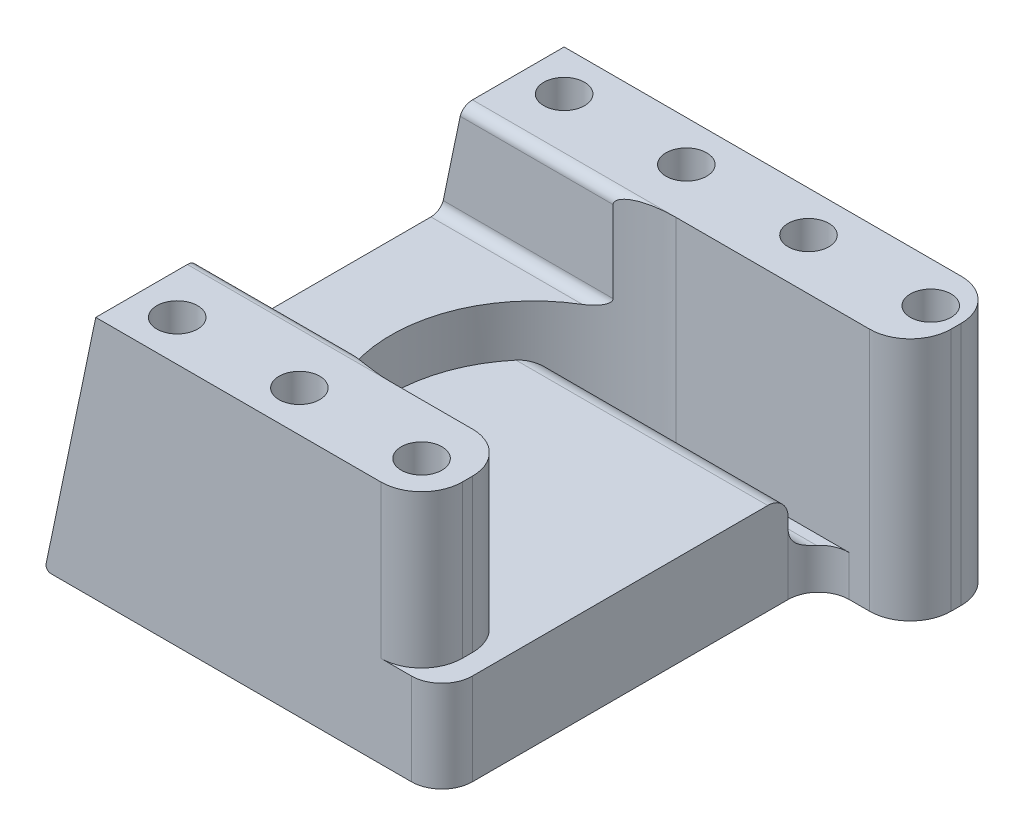
SolidWorks part; units mm, degrees
material "PEI"
ref_plane "Front Plane" through (0, 0, 0) normal (0, 0, 1) x (1, 0, 0)
ref_plane "Top Plane" through (0, 0, 0) normal (0, 1, 0) x (1, 0, 0)
ref_plane "Right Plane" through (0, 0, 0) normal (1, 0, 0) x (0, 0, -1)
sketch "Sketch2" plane through (0, 0, 0) normal (0, 1, 0) x (1, 0, 0)
  line L0 (0, 0) -> (0, 19)
  line L1 (0, 0) -> (-12, 0)
  line L2 (-12, 0) -> (-12, 19)
  line L3 (0, 0) -> (4, 0)
  line L4 (16, -23) -> (-16, -23)
  line L5 (16, -23) -> (16, 23)
  line L6 (16, 23) -> (-16, 23)
  line L7 (-16, -23) -> (-16, 23)
  line L8 (16, -23) -> (-16, 23) construction
  line L9 (16, 23) -> (-16, -23) construction
  line L10 (4, 14) -> (16, 14)
  line L11 (4, -14) -> (16, -14)
  line L12 (12, 19) -> (24.0037, 19)
  line L13 (16, 14) -> (27, 14)
  line L14 (16, 14) -> (16, 23)
  line L15 (16, 23) -> (27, 23)
  line L16 (27, 14) -> (27, 23)
  circle A0 centre (-12, 19) radius 2
  circle A1 centre (0, 19) radius 2
  circle A2 centre (12, 19) radius 2
  circle A4 centre (0, -19) radius 2
  circle A5 centre (-12, -19) radius 2
  circle A6 centre (4, 0) radius 14
  circle A7 centre (12, -19) radius 2
  circle A8 centre (24.0037, 19) radius 2
  dimension "D3" = 4
  dimension "D4" = 4
  dimension "D7" = 28
  dimension "D12" = 4
  dimension "D1" = 12
  dimension "D2" = 19
  dimension "D5" = 19
  dimension "D6" = 4
  dimension "D8" = 46
  dimension "D9" = 32
  dimension "D10" = 15
  dimension "D11" = 12.0037
extrude "Boss-Extrude1" add sketch "Sketch2" along normal blind 24 contours A6 L5 L6 L7 L4 A0 A1 A4 A2 A5 | A8 L5 L13 L16 L15 region at (-7.6743, 0, -8.7015) region at (21.136, 0, -18.4273)
sketch "Sketch4" plane through (0, 0, 23) normal (0, 0, 1) x (1, 0, 0)
  line L0 (-16, 0) -> (-21, 0)
  line L1 (-21, 0) -> (-16, 24)
  line L4 (-16, 0) -> (16, 0)
  line L5 (16, 0) -> (16, 24)
  line L6 (16, 24) -> (-16, 24)
  line L7 (-16, 24) -> (-16, 0)
  line L8 (-16, 0) -> (16, 0)
  line L10 (16, 24) -> (-16, 24)
  line L11 (-16, 24) -> (-16, 0)
  line L14 (16, 0) -> (16, 24)
  line M9 (-16, 24) -> (-16, 0)
  dimension "D2" = 5
  dimension "D1" = 0
extrude "Boss-Extrude2" add sketch "Sketch4" against normal up to surface (46 mm away) contours L1 L0 M9 region at (-17.6667, 8, 23) up to face at (5.5, 12, -23)
sketch "Sketch5" plane through (0, 24, 0) normal (0, 1, 0) x (1, 0, 0)
  line L0 (0, 0) -> (-21, 0)
  line L1 (0, 13) -> (-21, 13)
  line L2 (0, -13) -> (-21, -13)
  line L4 (-16, -23) -> (-16, 23)
  line L5 (-16, 23) -> (-21, 23)
  line L6 (-21, 23) -> (-21, -23)
  line L7 (-21, -23) -> (-16, -23)
  line L8 (-16, -23) -> (-16, 23)
  line L9 (-16, 23) -> (-21, 23)
  line L10 (-21, 23) -> (-21, -23)
  line L11 (-21, -23) -> (-16, -23)
  line L15 (4, 14) -> (27, 14)
  line L16 (16, -23) -> (16, -14)
  line L17 (27, 23) -> (-16, 23)
  line L18 (-16, 23) -> (-16, -23)
  line L19 (-16, -23) -> (16, -23)
  line L20 (27, 14) -> (27, 23)
  line L21 (27, 14) -> (27, 23)
  line L22 (4, 14) -> (27, 14)
  line L23 (16, -23) -> (16, -14)
  line L24 (27, 23) -> (-16, 23)
  line L25 (-16, 23) -> (-16, -23)
  line L26 (-16, -23) -> (16, -23)
  line L30 (16, -14) -> (4, -14)
  line L31 (16, -14) -> (4, -14)
  arc A1 (4, 14) -> (4, -14) centre (4, 0) ccw
  arc A2 (4, 14) -> (4, -14) centre (4, 0) ccw
  arc M16 (4, -14) -> (4, 14) centre (4, 0) cw
  line M20 (-16, 23) -> (-16, -23)
  dimension "D1" = 0
  dimension "D2" = 0
  dimension "D3" = 13
  dimension "D4" = 13
extrude "Cut-Extrude1" cut sketch "Sketch5" against normal blind 10 contours L1 L0 M16 M20 | L1 L10 L0 M20 | L2 L0 M16 M20 | L0 L10 L2 M20 region at (-11.4463, 24, 7.5042) region at (-11.4463, 24, -7.5042) region at (-18.5, 24, 6.5) region at (-18.5, 24, -6.5)
fillet "Fillet1" radius 1 4 edges at (-9.6397, 14, 13) (-9.6397, 14, -13) (-8.5981, 24, 13) (-8.5981, 24, -13)
fillet "Fillet2" radius 0.5 1 edges at (-21, 0, 0)
fillet "Fillet3" radius 4 4 edges at (16, 12, 14) (16, 12, 23) (27, 12, -23) (27, 12, -14)
sketch "Sketch6" plane through (0, 0, 0) normal (0, -1, 0) x (1, 0, 0)
  line L0 (18, 0) -> (18, -14)
  line L1 (18, 0) -> (18, 14)
  line L2 (12, 14) -> (18, 14)
  line L3 (12, 23) -> (18, 23)
  line L4 (18, 23) -> (18, 14)
  line L6 (4, 14) -> (12, 14)
  line L7 (12, 23) -> (-20.3851, 23)
  line L8 (-20.3851, 23) -> (-20.3851, -23)
  line L9 (-20.3851, -23) -> (23, -23)
  line L11 (23, -14) -> (4, -14)
  line L12 (4, 14) -> (12, 14)
  line L13 (12, 23) -> (-20.3851, 23)
  line L14 (-20.3851, 23) -> (-20.3851, -23)
  line L15 (-20.3851, -23) -> (23, -23)
  line L17 (23, -14) -> (4, -14)
  line L23 (27, -19) -> (27, -18)
  line L24 (27, -19) -> (27, -18)
  line L25 (16, 18) -> (16, 19)
  line L26 (16, 18) -> (16, 19)
  circle A0 centre (4, 0) radius 14
  arc A3 (12, 14) -> (16, 18) centre (12, 18) ccw
  arc A4 (16, 19) -> (12, 23) centre (12, 19) ccw
  arc A5 (4, 14) -> (4, -14) centre (4, 0) ccw
  arc A6 (12, 14) -> (16, 18) centre (12, 18) ccw
  arc A7 (16, 19) -> (12, 23) centre (12, 19) ccw
  arc A8 (4, 14) -> (4, -14) centre (4, 0) ccw
  arc A12 (23, -23) -> (27, -19) centre (23, -19) ccw
  arc A13 (23, -23) -> (27, -19) centre (23, -19) ccw
  arc A14 (27, -18) -> (23, -14) centre (23, -18) ccw
  arc A15 (27, -18) -> (23, -14) centre (23, -18) ccw
  line M10 (4, 14) -> (12, 14)
  arc M11 (12, 14) -> (16, 18) centre (12, 18) ccw
  arc M12 (16, 19) -> (12, 23) centre (12, 19) ccw
  line M17 (23, -14) -> (4, -14)
  arc M18 (4, -14) -> (4, 14) centre (4, 0) cw
  dimension "D1" = 0
extrude "Boss-Extrude3" add sketch "Sketch6" against normal blind 9 contours A0 L0 M17 | A0 M18 | L4 L3 L2 M12 M11 | A0 L1 L2 M10 region at (14.8728, 0, 10.8728) region at (4, 0, 0) region at (14.8728, 0, -10.8728) region at (16.4771, 0, 18.5)
fillet "Fillet4" radius 3 2 edges at (18, 4.5, 23) (18, 4.5, -14)
sketch "Sketch7" plane through (0, 9, 0) normal (0, 1, 0) x (1, 0, 0)
  line L0 (18, 11) -> (-4.6603, 11)
  line L5 (12, -23) -> (15, -23)
  line L6 (18, -20) -> (18, 11)
  line L7 (21, 14) -> (4, 14)
  line L8 (4, -14) -> (12, -14)
  line L9 (16, -18) -> (16, -19)
  line L10 (12, -23) -> (15, -23)
  line L11 (18, -20) -> (18, 11)
  line L12 (21, 14) -> (4, 14)
  line L13 (4, -14) -> (12, -14)
  line L14 (16, -18) -> (16, -19)
  arc A5 (15, -23) -> (18, -20) centre (15, -20) ccw
  arc A6 (21, 14) -> (18, 11) centre (21, 11) ccw
  arc A7 (4, 14) -> (4, -14) centre (4, 0) ccw
  arc A8 (16, -18) -> (12, -14) centre (12, -18) ccw
  arc A9 (12, -23) -> (16, -19) centre (12, -19) ccw
  arc A10 (15, -23) -> (18, -20) centre (15, -20) ccw
  arc A11 (21, 14) -> (18, 11) centre (21, 11) ccw
  arc A12 (4, 14) -> (4, -14) centre (4, 0) ccw
  arc A13 (16, -18) -> (12, -14) centre (12, -18) ccw
  arc A14 (12, -23) -> (16, -19) centre (12, -19) ccw
  arc M14 (18, 11) -> (21, 14) centre (21, 11) cw
  line M15 (21, 14) -> (4, 14)
  arc M16 (4, 14) -> (4, -14) centre (4, 0) ccw
  dimension "D1" = 0
extrude "Cut-Extrude2" cut sketch "Sketch7" against normal blind 5 contours L0 M14 M15 M16 region at (8.2788, 9, -12.4431)
fillet "Fillet5" radius 2 2 edges at (6.6699, 4, -11) (6.6699, 9, -11)
